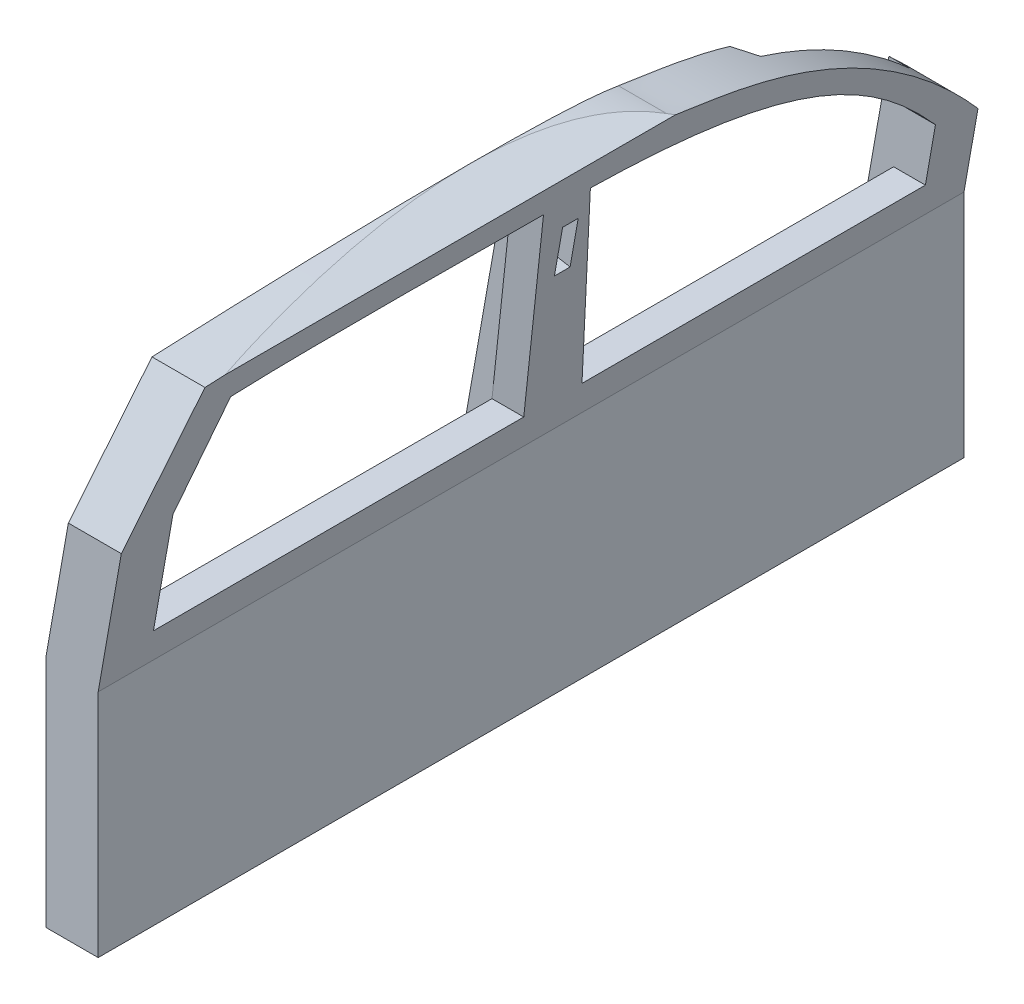
SolidWorks part; units mm, degrees
ref_plane "정면" through (0, 0, 0) normal (0, 0, 1) x (1, 0, 0)
ref_plane "윗면" through (0, 0, 0) normal (0, 1, 0) x (1, 0, 0)
ref_plane "우측면" through (0, 0, 0) normal (1, 0, 0) x (0, 0, -1)
sketch "스케치1" plane through (0, 0, 0) normal (1, 0, 0) x (0, 0, -1)
  line L0 (-3.3731, 1.3955) -> (806.6253, -0.2335) construction
  line L3 (-43.6818, -318.771) -> (786.3182, -318.771)
  line L4 (786.3182, -318.771) -> (786.3182, -22.0843)
  line L5 (15.5599, 146.5134) -> (-43.6818, 27.7051)
  line L6 (-43.6818, 27.7051) -> (-43.6818, -318.771)
  line L7 (44.4616, 122.2817) -> (4.1166, 37.2053)
  line L8 (4.1166, 37.2053) -> (4.1166, -68.771)
  line L9 (744.1166, -68.771) -> (414.9329, -68.771)
  line L10 (344.1304, 123.5979) -> (359.1166, -68.771)
  line L11 (389.1166, 123.2665) -> (414.9329, -68.771)
  line L12 (744.1166, -68.771) -> (744.1166, -13.771)
  line L13 (359.1166, -68.771) -> (4.1166, -68.771)
  line L14 (-118.6341, 156.229) -> (936.2893, 156.229) construction
  line L15 (-483.5029, 124.6259) -> (663.2942, 124.6259) construction
  spline S0 degree 3 poles (786.3182, -22.0843) (649.945, 130.0043) (517.545, 136.9962) (462.3521, 148.3504) knots 0 0 0 0 1 1 1 1
  spline S1 degree 3 poles (15.5599, 146.5134) (105.2239, 151.5262) (383.0558, 164.5678) (462.3521, 148.3504) knots 0 0 0 0 1 1 1 1
  spline S2 degree 3 poles (44.4616, 122.2817) (125.6423, 126.6425) (305.7634, 123.6569) (389.1166, 123.2665) knots 0 0 0 0 1 1 1 1
  spline S3 degree 3 poles (389.1166, 123.2665) (584.5975, 118.8361) (668.4477, 69.762) (744.1166, -13.771) knots 0.027736 0.027736 0.027736 0.027736 0.84207 0.84207 0.84207 0.84207
  point P19 (0, 0)
  point P21 (744.1166, -68.771)
  point P23 (446.8023, 143.6287)
  point P24 (786.1976, -22.0113)
  point P25 (24.9768, 133.6165)
  point P26 (475.9708, 127.5083)
  point P27 (0, 0)
  point P28 (24.5508, 134.6101)
  point P29 (462.3521, 148.3504)
  dimension "D7" = 830
  dimension "D1" = 810
  dimension "D2" = 355
  dimension "D3" = 192.0375
  dimension "D4" = 191.0527
  dimension "D5" = 355
  dimension "D6" = 250
  dimension "D8" = 30
  dimension "D9" = 55
  dimension "D11" = 475
extrude "보스-돌출1" add sketch "스케치1" along normal blind 300 contours L0 L6 L3 L4 S0 L12 L9 L11 L10 L13 L8 | L6 L0 L8 L7 S2 L10 L11 S3 L12 S0 S1 L5 region at (0, -149.6957, -363.1779)
sketch "스케치2" plane through (0, 0, 43.6818) normal (0, 0, 1) x (1, 0, 0)
  line L0 (139.3995, 156.229) -> (139.3995, -318.771) construction
  line L1 (300, 156.229) -> (0, 156.229) construction
  line L2 (300, -318.771) -> (0, -318.771) construction
  line L3 (139.3995, 156.229) -> (95.3177, -93.771)
  line L4 (95.3177, -93.771) -> (95.3177, -318.771)
  line L5 (139.3995, 156.229) -> (188.6399, 147.5466)
  line L6 (188.6399, 147.5466) -> (145.3177, -98.1455)
  line L7 (145.3177, -98.1455) -> (145.3177, -318.771)
  line L8 (139.3995, 156.229) -> (55.6441, -318.771) construction
  line L9 (0, -318.771) -> (341.3647, -318.771)
  line L10 (0, -318.771) -> (0, 251.4574)
  line L11 (0, 251.4574) -> (341.3647, 251.4574)
  line L12 (341.3647, -318.771) -> (341.3647, 251.4574)
  line L13 (145.3177, -98.1455) -> (96.0773, -89.463) construction
  line L14 (145.3177, -98.1455) -> (95.3177, -98.1455) construction
  line M5 (0, 27.7051) -> (0, -318.771)
  line M6 (0, -318.771) -> (300, -318.771)
  line M7 (300, -318.771) -> (300, 27.7051)
  line M8 (300, 27.7051) -> (0, 27.7051)
  dimension "D1" = 50
  dimension "D2" = 10
  dimension "D3" = 50
extrude "컷-돌출1" cut sketch "스케치2" against normal through all both and the other way through all contours L9 L12 L11 L10 L3 L5 L6 M8 M7 | L4 L3 M8 M5 M6 | L6 L7 M6 M7 M8 region at (197.4885, 94.8877, 43.6818) region at (49.7358, -140.5018, 43.6818) region at (224.53, -149.0451, 43.6818)
sketch "스케치4" plane through (108.4793, -19.1278, 0) normal (-0.9848, 0.1736, 0) x (0, 0, 1)
  line L0 (-389.1166, 129.591) -> (-359.1166, 129.591) construction
  line L2 (-744.1166, -50.409) -> (-744.1166, 144.591)
  line L3 (-744.1166, 144.591) -> (-389.1166, 144.591)
  line L4 (-389.1166, 17.9899) -> (-389.1166, 144.591)
  line L6 (-359.1166, -50.409) -> (-359.1166, 144.591)
  line L7 (-359.1166, 144.591) -> (-4.1166, 144.591)
  line L8 (-4.1166, -50.409) -> (-4.1166, 144.591)
  line L9 (-381.6166, 129.591) -> (-366.6166, 129.591)
  line L10 (-381.6166, 129.591) -> (-381.6166, 84.591)
  line L11 (-381.6166, 84.591) -> (-366.6166, 84.591)
  line L12 (-366.6166, 129.591) -> (-366.6166, 84.591)
  line L13 (-744.1166, -50.409) -> (-744.1166, -80.409)
  line L14 (-744.1166, -80.409) -> (-389.1166, -80.409)
  line L15 (-389.1166, -80.409) -> (-389.1166, 17.9899)
  line L16 (-359.1166, -50.409) -> (-359.1166, -80.409)
  line L17 (-359.1166, -80.409) -> (-4.1166, -80.409)
  line L18 (-4.1166, -80.409) -> (-4.1166, -50.409)
  point P16 (-374.1166, 129.591)
  point P17 (-374.1166, 129.591)
  point P22 (0, 0)
  point P25 (0, 0)
  line M4 (-414.9329, -50.409) -> (-744.1166, -50.409)
  line M5 (-744.1166, -50.409) -> (-744.1166, 5.4394)
  line M7 (-389.1166, 144.591) -> (-414.9329, -50.409)
  line M8 (-4.1166, -50.409) -> (-359.1166, -50.409)
  line M9 (-359.1166, -50.409) -> (-344.1304, 144.9275)
  line M11 (-44.4616, 143.591) -> (-4.1166, 57.2022)
  line M12 (-4.1166, 57.2022) -> (-4.1166, -50.409)
  line M15 (-786.3182, -75.7947) -> (43.6818, -75.7947)
  dimension "D1" = 355
  dimension "D2" = 195
  dimension "D3" = 195
  dimension "D4" = 355
  dimension "D5" = 15
  dimension "D6" = 45
  dimension "D7" = 195
  dimension "15" = 15
  dimension "90" = 90
  dimension "225" = 225
  dimension "D8" = 225
extrude "컷-돌출2" cut sketch "스케치4" against normal through all contours L10 L11 L12 L9
extrude "컷-돌출3" cut sketch "스케치4<4>" against normal blind 20 contours M4 M7 M5 | L3 L2 | L3 L2 | L15 L4 L13 M15 M7 M4 | L18 L16 M15 M8 | L7 L6 M9 | L8 L7 M11 | L7 M9 M8 M12 M11 region at (97.5218, -81.271, -181.6166) region at (99.0003, -72.886, -579.5248) region at (116.8695, 28.4554, -572.9895) region at (116.5351, 26.5588, -177.9033) region at (122.3002, 59.254, -354.1298)
sketch "스케치4<4>" plane through (108.4793, -19.1278, 0) normal (-0.9848, 0.1736, 0) x (0, 0, 1) same geometry as "스케치4"
